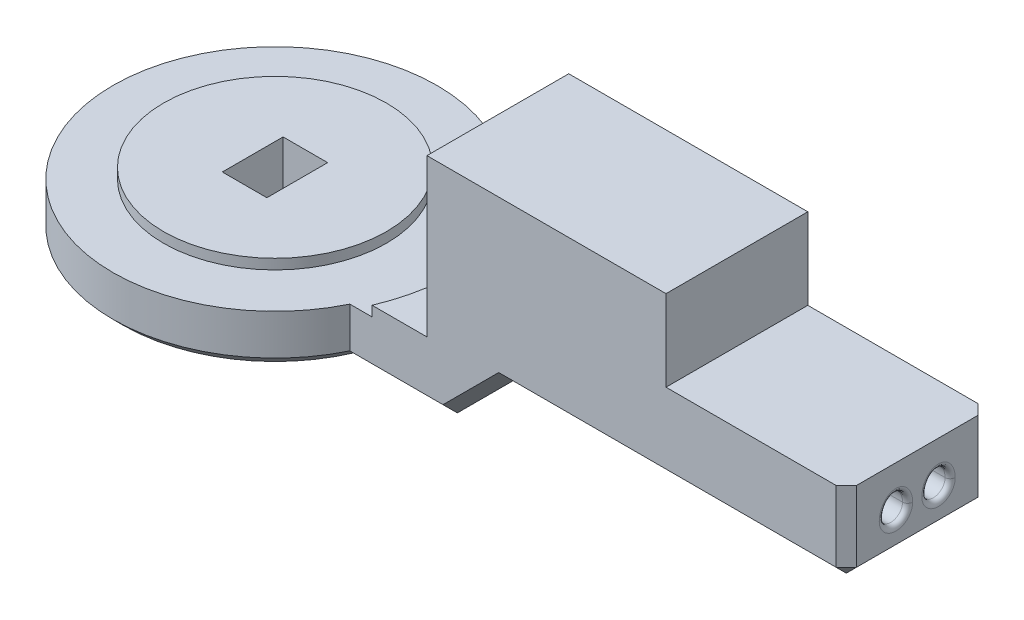
SolidWorks part; units mm, degrees
ref_plane "Front Plane" through (0, 0, 0) normal (0, 0, 1) x (1, 0, 0)
ref_plane "Top Plane" through (0, 0, 0) normal (0, 1, 0) x (1, 0, 0)
ref_plane "Right Plane" through (0, 0, 0) normal (1, 0, 0) x (0, 0, -1)
sketch "Sketch1" plane through (0, 0, 0) normal (0, 1, 0) x (1, 0, 0)
  line L0 (-1.1, 1.0198) -> (-1.1, -1.0198)
  line L1 (1.1, 1.0198) -> (1.1, -1.0198)
  line L2 (-998.0463, -3.5) -> (49001.9537, -3.5) construction
  line L3 (-998.5569, 3.5) -> (49001.4431, 3.5) construction
  line L4 (27.8, -1002.9744) -> (27.8, 48997.0256) construction
  line L5 (7.1937, 3.5) -> (27.8, 3.5)
  line L6 (27.8, 3.5) -> (27.8, -3.5)
  line L7 (27.8, -3.5) -> (7.1937, -3.5)
  line L8 (0.887, 1.2096) -> (1.1, 1.5) construction
  line L9 (-1.1, 1.5) -> (1.1, 1.5)
  line L10 (-1.1, 1.5) -> (-1.1, -1.5)
  line L11 (-1.1, -1.5) -> (1.1, -1.5)
  line L12 (1.1, 1.5) -> (1.1, -1.5)
  line L13 (-0.887, 1.2096) -> (1.1, -1.5) construction
  line L14 (-1.1, -1.5) -> (0.887, 1.2096) construction
  line L15 (-1.1, 1.5) -> (-0.887, 1.2096) construction
  arc A0 (-1.1, -1.0198) -> (-0.887, -1.2096) centre (0, 0) ccw construction
  arc A1 (-1.1, 1.0198) -> (-1.1, -1.0198) centre (0, 0) ccw construction
  arc A2 (1.1, -1.0198) -> (1.1, 1.0198) centre (0, 0) ccw construction
  arc A3 (-0.887, 1.2096) -> (-1.1, 1.0198) centre (0, 0) ccw construction
  arc A4 (7.1937, 3.5) -> (7.1937, -3.5) centre (0, 0) ccw
  arc A5 (7.1937, -3.5) -> (7.1937, 3.5) centre (0, 0) ccw construction
  arc A6 (-0.887, -1.2096) -> (0, -1.5) centre (0, 0) ccw construction
  arc A7 (0.887, -1.2096) -> (1.1, -1.0198) centre (0, 0) ccw construction
  arc A8 (0, -1.5) -> (0.887, -1.2096) centre (0, 0) ccw construction
  arc A9 (1.1, 1.0198) -> (0.887, 1.2096) centre (0, 0) ccw construction
  arc A10 (0.887, 1.2096) -> (0, 1.5) centre (0, 0) ccw construction
  arc A11 (0, 1.5) -> (-0.887, 1.2096) centre (0, 0) ccw construction
  dimension "D1" = 3
  dimension "D4" = 16
  dimension "D2" = 1.1
  dimension "D3" = 1.1
  dimension "D5" = 3.5
  dimension "D6" = 3.5
  dimension "D7" = 27.8
extrude "Boss-Extrude1" add sketch "Sketch1" against normal blind 3 contours L5 A4 L7 L6 L9 L12 L1 L11 L10 L0 region at (7.4506, 0, 0)
sketch "Sketch2" plane through (0, 0, 0) normal (0, 1, 0) x (1, 0, 0)
  circle A0 centre (0, 0) radius 9
  circle A1 centre (0, 0) radius 5.5
  dimension "D1" = 18
  dimension "D2" = 3.5
extrude "Cut-Extrude1" cut sketch "Sketch2" against normal blind 0.5
sketch "Sketch3" plane through (0, 0, 0) normal (0, 1, 0) x (1, 0, 0)
  line L1 (27.8, 3.5) -> (11, 3.5)
  line L2 (27.8, 3.5) -> (27.8, -3.5)
  line L3 (27.8, -3.5) -> (11, -3.5)
  line L4 (11, 3.5) -> (11, -3.5)
  line L5 (27.8, -3.5) -> (8.2916, -3.5) construction
  dimension "D1" = 11
extrude "Boss-Extrude2" add sketch "Sketch3" along normal blind 3.75
sketch "Sketch5" plane through (0, -3, 0) normal (0, -1, 0) x (1, 0, 0)
  line L0 (27.8, -3.5) -> (31.7, -3.5)
  line L1 (27.8, 3.5) -> (31.7, 3.5)
  line L2 (31.7, 3.5) -> (31.7, -3.5)
  line L3 (27.8, 3.5) -> (27.8, -3.5)
  dimension "D1" = 3.9
extrude "Boss-Extrude3" add sketch "Sketch5" against normal up to vertex (6.75 mm away) up to point (27.8, 3.75, 3.5)
sketch "Sketch6" plane through (11, 0, 0) normal (-1, 0, 0) x (0, 0, 1)
  line L0 (6.5, 1.65) -> (-6.5, 1.65) construction
  line L4 (-3.5, 0) -> (3.5, 0) construction
  arc A0 (0.475, 1.65) -> (1.625, 1.65) centre (1.05, 1.65) ccw
  arc A1 (-1.625, 1.65) -> (-0.475, 1.65) centre (-1.05, 1.65) ccw
  arc A2 (1.625, 1.65) -> (0.475, 1.65) centre (1.05, 1.65) ccw construction
  arc A3 (-0.475, 1.65) -> (-1.625, 1.65) centre (-1.05, 1.65) ccw construction
  ellipse E0 centre (-1.05, 1.65) end of major axis (-1.05, 2.4) minor radius 0.575 (-0.475, 1.65) -> (-1.625, 1.65) ccw
  ellipse E1 centre (1.05, 1.65) end of major axis (1.05, 2.4) minor radius 0.575 (1.625, 1.65) -> (0.475, 1.65) ccw
  ellipse E2 centre (-1.05, 1.65) end of major axis (-1.05, 2.4) minor radius 0.575 (-1.625, 1.65) -> (-0.475, 1.65) ccw construction
  ellipse E3 centre (1.05, 1.65) end of major axis (1.05, 2.4) minor radius 0.575 (0.475, 1.65) -> (1.625, 1.65) ccw construction
  dimension "D1" = 1.15
  dimension "D2" = 1.15
  dimension "D3" = 2.1
  dimension "D4" = 1.05
  dimension "D5" = 1.65
  dimension "D6" = 0.75
  dimension "D7" = 0.75
extrude "Cut-Extrude3" cut sketch "Sketch6" against normal through all
fillet "Fillet2" radius 0.25 8 edges at (11, 1.075, -1.05) (31.7, 1.075, -1.05) (11, 1.075, 1.05) (31.7, 1.075, 1.05) (31.7, 2.4, -1.05) (11, 2.4, -1.05) (31.7, 2.4, 1.05) (11, 2.4, 1.05)
sketch "Sketch7" plane through (0, 3.75, 0) normal (0, 1, 0) x (1, 0, 0)
  line L0 (11, -3.5) -> (31.7, -3.5) construction
  line L1 (11, 3.5) -> (22.8, 3.5)
  line L2 (11, 3.5) -> (11, -3.5)
  line L3 (11, -3.5) -> (22.8, -3.5)
  line L4 (22.8, 3.5) -> (22.8, -3.5)
  dimension "D1" = 11.8
extrude "Boss-Extrude4" add sketch "Sketch7" along normal blind 4
sketch "Sketch9" plane through (0, -3, 0) normal (0, -1, 0) x (-1, 0, 0)
  line L0 (-7.1937, 3.5) -> (-31.7, 3.5) construction
  line L1 (-31.7, -3.5) -> (-12, -3.5)
  line L2 (-31.7, -3.5) -> (-31.7, 3.5)
  line L3 (-31.7, 3.5) -> (-12, 3.5)
  line L4 (-12, -3.5) -> (-12, 3.5)
  dimension "D1" = 12
extrude "Cut-Extrude5" cut sketch "Sketch9" against normal blind 2.75
chamfer "Chamfer2" distance 2.75 angle 45 1 edges at (12, -0.25, 0)
chamfer "Chamfer1" distance 0.5 14 edges at (31.7, 1.75, -3.5) (31.7, 1.75, 3.5) (-8, -3, 0) (9.5969, -3, -3.5) (9.5969, -3, 3.5) (0, -3, -1.5) (-1.1, -3, 0) (0, -3, 1.5) (1.1, -3, 0) (31.7, -0.25, 0) (23.225, -0.25, -3.5) (13.375, -1.625, -3.5) (13.375, -1.625, 3.5) (23.225, -0.25, 3.5)
